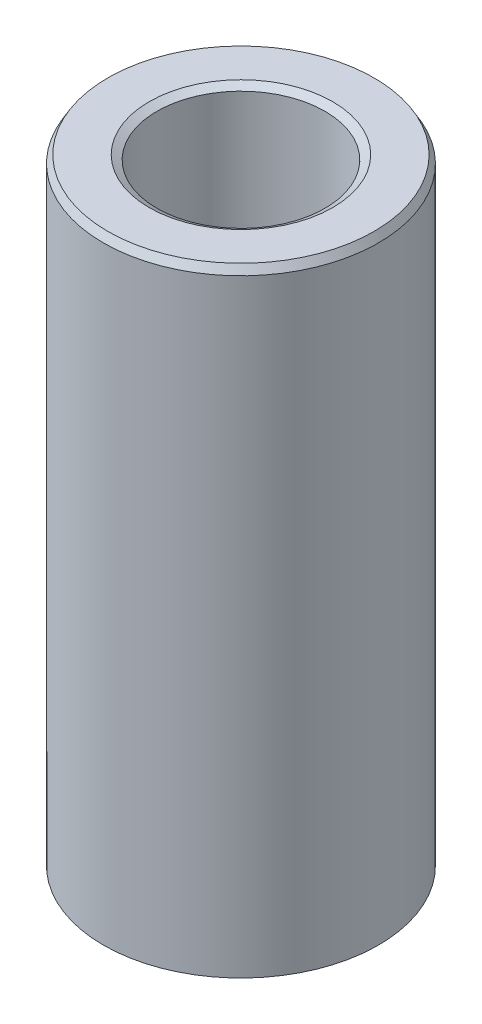
SolidWorks part; units mm, degrees
ref_plane "Front Plane" through (0, 0, 0) normal (0, 0, 1) x (1, 0, 0)
ref_plane "Top Plane" through (0, 0, 0) normal (0, 1, 0) x (1, 0, 0)
ref_plane "Right Plane" through (0, 0, 0) normal (1, 0, 0) x (0, 0, -1)
sketch "Sketch1" plane through (0, 0, 0) normal (0, 1, 0) x (1, 0, 0)
  circle A0 centre (0, 0) radius 12.5
  dimension "SLEEVE_OD" = 25
extrude "Boss-Extrude1" add sketch "Sketch1" along normal blind 56.3849
sketch "Sketch2" plane through (0, 0, 0) normal (0, 1, 0) x (1, 0, 0)
  circle A0 centre (0, 0) radius 7.6407
  dimension "BORE_D" = 15.2814
extrude "Cut-Extrude1" cut sketch "Sketch2" along normal through all
chamfer "Chamfer1" distance 0.7007 angle 30 4 edges at (0, 56.3849, 7.6407) (0, 0, 7.6407) (0, 0, 12.5) (0, 56.3849, 12.5) first distance on face at (0, 56.3849, 7.6407) first distance on face at (0, 0, 7.6407) first distance on face at (0, 56.3849, 12.5)
